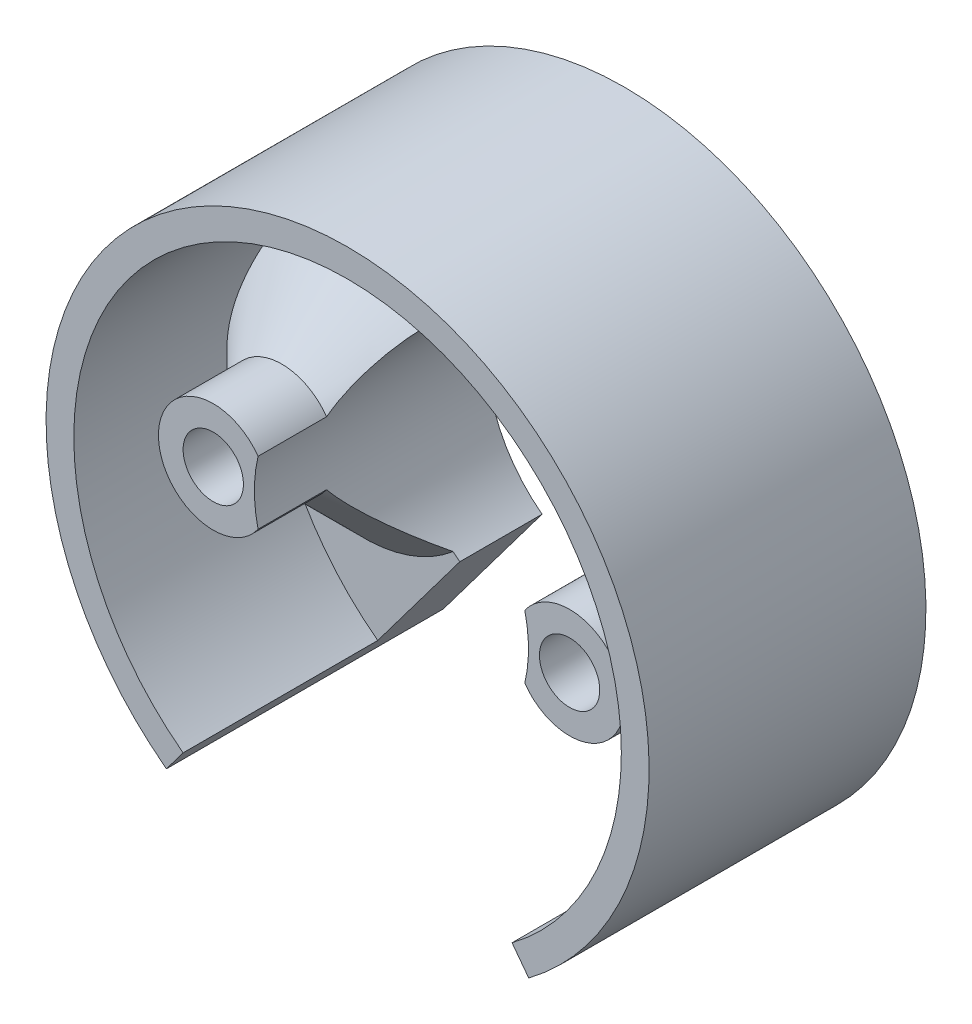
SolidWorks part; units mm, degrees
ref_plane "前视基准面" through (0, 0, 0) normal (0, 0, 1) x (1, 0, 0)
ref_plane "上视基准面" through (0, 0, 0) normal (0, 1, 0) x (1, 0, 0)
ref_plane "右视基准面" through (0, 0, 0) normal (1, 0, 0) x (0, 0, -1)
sketch "草图1" plane through (0, 0, 0) normal (0, 0, 1) x (1, 0, 0)
  circle A4 centre (0, 0) radius 5
  circle A5 centre (0, 0) radius 11
  circle A6 centre (-6.5, 0) radius 1.1
  circle A7 centre (6.5, 0) radius 1.1
  dimension "D1" = 22
  dimension "D2" = 10
  dimension "D3" = 2.2
extrude "凸台-拉伸1" add sketch "草图1" along normal blind 3
sketch "草图2" plane through (0, 0, 3) normal (0, 0, 1) x (1, 0, 0)
  arc A0 (4.8654, -1.1524) -> (4.8654, 1.1524) centre (6.5, 0) ccw
  arc A1 (-4.8654, 1.1524) -> (-4.8654, -1.1524) centre (-6.5, 0) ccw
  arc A2 (4.8654, -1.1524) -> (4.8654, 1.1524) centre (0, 0) ccw
  circle A4 centre (0, 0) radius 5 construction
  arc A5 (-4.8654, 1.1524) -> (-4.8654, -1.1524) centre (0, 0) ccw
  dimension "D1" = 4
extrude "凸台-拉伸2" add sketch "草图2" along normal blind 5.5
sketch "草图3" plane through (0, 0, 3) normal (0, 0, 1) x (1, 0, 0)
  line L0 (-6.6084, -8.7937) -> (-6, -7.9841)
  line L1 (6.6084, -8.7937) -> (6, -7.9841)
  line L2 (0, 11) -> (0, 9.9873) construction
  circle A0 centre (0, 0) radius 11 construction
  arc A1 (6.6084, -8.7937) -> (-6.6084, -8.7937) centre (0, 0) ccw
  arc A3 (6, -7.9841) -> (-6, -7.9841) centre (0, 0) ccw
  dimension "D1" = 11
  dimension "D2" = 9.9873
  dimension "D3" = 12
extrude "凸台-拉伸3" add sketch "草图3" along normal blind 7.1
chamfer "倒角1" distance 3 angle 45 2 edges at (8.5, 0, 3) (-8.5, 0, 3)
sketch "草图4" plane through (0, 0, 0) normal (0, 0, -1) x (-1, 0, 0)
  line L0 (6.6084, -8.7937) -> (6, -7.9841) construction
  line L1 (-6, -7.9841) -> (-6.6084, -8.7937) construction
  line L2 (6.6084, -8.7937) -> (3.0038, -3.9971)
  line L3 (-3.0038, -3.9971) -> (-6.6084, -8.7937)
  circle A0 centre (0, 0) radius 5 construction
  circle A1 centre (0, 0) radius 11
  circle A2 centre (0, 0) radius 11
  circle A3 centre (0, 0) radius 5
  circle M3 centre (0, 0) radius 11
  circle M4 centre (0, 0) radius 5
  dimension "D1" = 0
extrude "切除-拉伸1" cut sketch "草图4" against normal blind 10 contours L3 L2 M4 M3 region at (0, -7.8072, 0)
sketch "草图5" plane through (0, 0, 3) normal (0, 0, -1) x (-1, 0, 0)
  circle A0 centre (6.5, 0) radius 1.1 construction
  circle A1 centre (-6.5, 0) radius 1.1 construction
  circle A2 centre (6.5, 0) radius 1.1
  circle A3 centre (-6.5, 0) radius 1.1
extrude "切除-拉伸2" cut sketch "草图5" against normal up to next
